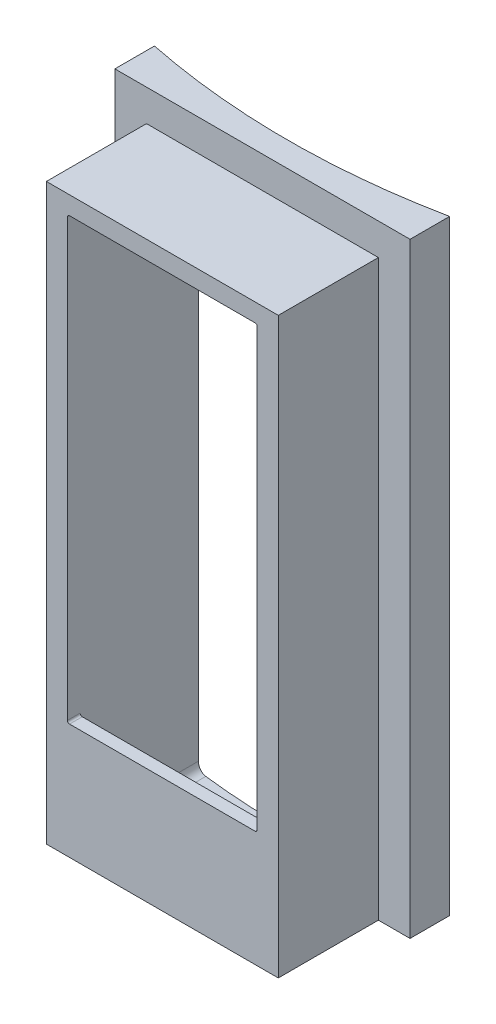
SolidWorks part; units mm, degrees
ref_plane "Front Plane" through (0, 0, 0) normal (0, 0, 1) x (1, 0, 0)
ref_plane "Top Plane" through (0, 0, 0) normal (0, 1, 0) x (1, 0, 0)
ref_plane "Right Plane" through (0, 0, 0) normal (1, 0, 0) x (0, 0, -1)
sketch "Sketch1" plane through (0, 0, 0) normal (0, 0, 1) x (1, 0, 0)
  line L1 (-44.45, 82.169) -> (44.45, 82.169)
  line L2 (-44.45, 82.169) -> (-44.45, -100.203)
  line L3 (-44.45, -100.203) -> (44.45, -100.203)
  line L4 (44.45, 82.169) -> (44.45, -100.203)
  point P5 (0, 82.169)
  dimension "D1" = 88.9
extrude "Extrude1" add sketch "Sketch1" along normal blind 230.2002
sketch "Sketch5" plane through (0, 0, 230.2002) normal (0, 0, 1) x (1, 0, 0)
  line L0 (44.45, 82.169) -> (-44.45, 82.169) construction
  line L1 (-34.925, 72.644) -> (34.925, 72.644)
  line L2 (-34.925, 72.644) -> (-34.925, -100.203)
  line L3 (-34.925, -100.203) -> (34.925, -100.203)
  line L4 (34.925, 72.644) -> (34.925, -100.203)
  line L5 (0, 82.169) -> (0, -100.203) construction
  point P4 (0, -100.203)
  point P5 (0, 82.169)
  point P11 (0, 72.644)
  dimension "D1" = 69.85
extrude "Extrude4" add sketch "Sketch5" along normal blind 30.1523
sketch "Sketch2" plane through (0, 82.169, 0) normal (0, 1, 0) x (-1, 0, 0)
  line L0 (-44.45, 0) -> (44.45, 0) construction
  circle A1 centre (0, 0) radius 222.758
sketch "Sketch4" plane through (0, 0, 230.2002) normal (0, 0, 1) x (1, 0, 0)
  line L1 (-28.575, 67.183) -> (28.575, 67.183)
  line L2 (-28.575, 67.183) -> (-28.575, -65.405)
  line L3 (-28.575, -65.405) -> (28.575, -65.405)
  line L4 (28.575, 67.183) -> (28.575, -65.405)
  point P4 (0, -65.405)
  point P5 (0, 67.183)
  point P6 (0, 0)
  dimension "D1" = 57.15
extrude "Extrude2" cut sketch "Sketch4" against normal blind 273.8502 and the other way blind 93.98
sketch "Sketch6" plane through (0, 0, 0) normal (0, 0, -1) x (-1, 0, 0)
  line L0 (-28.575, -65.405) -> (28.575, -65.405) construction
  line L1 (-28.575, -65.405) -> (28.575, -65.405)
  line L2 (-28.575, -65.405) -> (-28.575, -97.663)
  line L3 (-28.575, -97.663) -> (28.575, -97.663)
  line L4 (28.575, -65.405) -> (28.575, -97.663)
  line L6 (-28.575, 67.183) -> (28.575, 67.183)
  line L7 (-28.575, 67.183) -> (-28.575, 70.104)
  line L8 (-28.575, 70.104) -> (28.575, 70.104)
  line L9 (28.575, 67.183) -> (28.575, 70.104)
  line L10 (44.45, -100.203) -> (-44.45, -100.203) construction
  line L11 (-44.45, 82.169) -> (44.45, 82.169) construction
  point P4 (0, -100.203)
  point P6 (0, -65.405)
  point P13 (0, -100.203)
  point P15 (0, 82.169)
  point P19 (0, 67.183)
  point P22 (0, -97.663)
  dimension "D1" = 57.15
extrude "Extrude5" cut sketch "Sketch6" against normal blind 256.54
fillet "Fillet1" radius 2.54 4 edges at (-28.575, -97.663, 128.27) (28.575, -97.663, 128.27) (-28.575, 70.104, 128.27) (28.575, 70.104, 128.27)
extrude "Extrude3" cut sketch "Sketch2" against normal blind 202.86
sketch "Sketch7" plane through (0, 0, 260.3525) normal (0, 0, 1) x (1, 0, 0)
fillet "Fillet2" radius 0.635 4 edges at (28.575, 67.183, 258.4463) (-28.575, 67.183, 258.4463) (-28.575, -65.405, 258.4463) (28.575, -65.405, 258.4463)
sketch "Sketch8" plane through (0, 0, 260.3525) normal (0, 0, 1) x (1, 0, 0)
